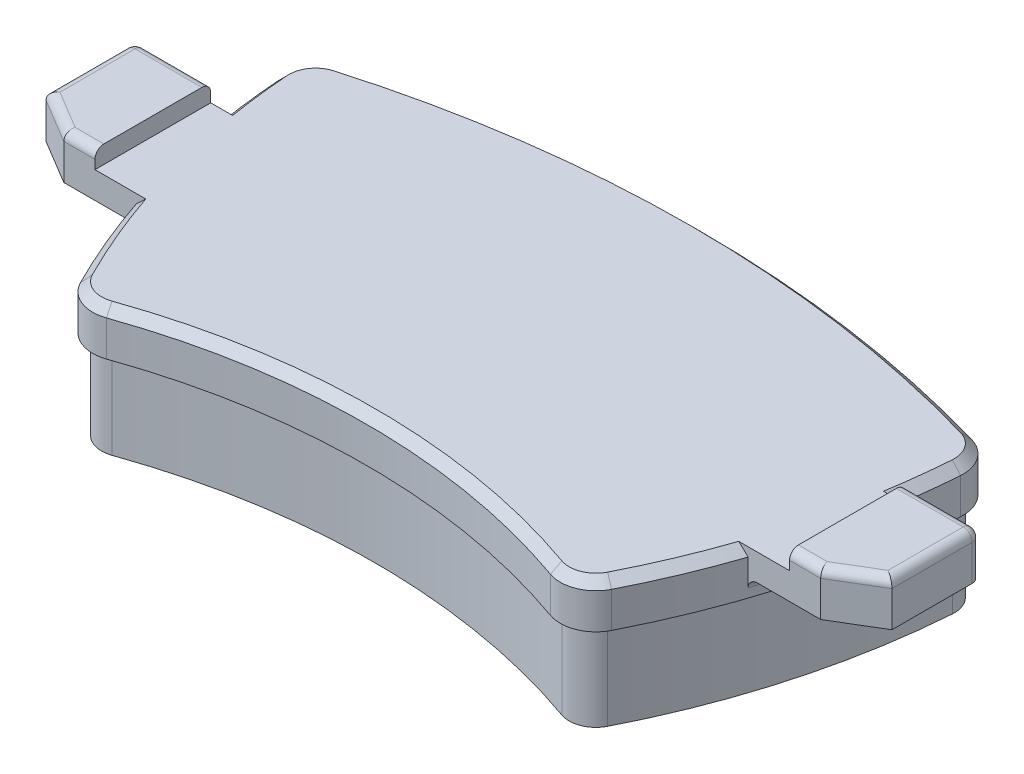
SolidWorks part; units mm, degrees
ref_plane "Front Plane" through (0, 0, 0) normal (0, 0, 1) x (1, 0, 0)
ref_plane "Top Plane" through (0, 0, 0) normal (0, 1, 0) x (1, 0, 0)
ref_plane "Right Plane" through (0, 0, 0) normal (1, 0, 0) x (0, 0, -1)
sketch "Szkic1" plane through (0, 0, 0) normal (0, 1, 0) x (1, 0, 0)
  line L0 (0, -17.533) -> (0, 17.533) construction
  line L5 (-37.5, -17.533) -> (37.5, 17.533) construction
  line L6 (-37.5, 17.533) -> (37.5, -17.533) construction
  line L8 (-37.5749, -16.8044) -> (37.5749, -16.8044)
  line L9 (-37.5749, -16.8044) -> (-37.5749, 23.1956)
  line L10 (-37.5749, 23.1956) -> (37.5749, 23.1956)
  line L11 (37.5749, -16.8044) -> (37.5749, 23.1956)
  arc A0 (-35.1983, 18.2205) -> (35.1983, 18.2205) centre (0, -103.8044) cw
  arc A1 (-28.9322, -15.1612) -> (-37.3587, 15.1176) centre (42.3641, 20.9925) cw
  arc A2 (28.9322, -15.1612) -> (37.3587, 15.1176) centre (-42.3641, 20.9925) ccw
  arc A3 (-25.2594, -16.6338) -> (25.2594, -16.6338) centre (0, -88.3134) cw
  arc A4 (35.1983, 18.2205) -> (37.3587, 15.1176) centre (34.3668, 15.3381) cw
  arc A5 (25.2594, -16.6338) -> (28.9322, -15.1612) centre (26.2565, -13.8044) ccw
  arc A6 (-28.9322, -15.1612) -> (-25.2594, -16.6338) centre (-26.2565, -13.8044) ccw
  arc A7 (-37.3587, 15.1176) -> (-35.1983, 18.2205) centre (-34.3668, 15.3381) cw
  point P0 (0, 0)
  point P6 (27.679, -17.533)
  point P8 (-27.679, -17.533)
  point P21 (27.679, -17.533)
  point P24 (-27.679, -17.533)
  dimension "D3" = 3
  dimension "D5" = 79.939
  dimension "D4" = 127
  dimension "D6" = 76
  dimension "D1" = 75
  dimension "D7" = 26.2565
  dimension "D8" = 75.1498
  dimension "D9" = 40
extrude "Dodanie-wyciągnięcie2" add sketch "Szkic1" along normal blind 10 contours A0 A4 A2 A5 A3 A6 A1 A7
sketch "Szkic3" plane through (0, 10, 0) normal (0, 1, 0) x (1, 0, 0)
  arc A16 (-35.4754, 19.1814) -> (-38.356, 15.0441) centre (-34.3668, 15.3381) ccw
  arc A17 (-38.356, 15.0441) -> (-29.824, -15.6134) centre (42.3641, 20.9925) ccw
  arc A18 (-29.824, -15.6134) -> (-24.9271, -17.577) centre (-26.2565, -13.8044) ccw
  arc A19 (24.9271, -17.577) -> (-24.9271, -17.577) centre (0, -88.3134) ccw
  arc A20 (24.9271, -17.577) -> (29.824, -15.6134) centre (26.2565, -13.8044) ccw
  arc A21 (29.824, -15.6134) -> (38.356, 15.0441) centre (-42.3641, 20.9925) ccw
  arc A22 (38.356, 15.0441) -> (35.4754, 19.1814) centre (34.3668, 15.3381) ccw
  arc A23 (35.4754, 19.1814) -> (-35.4754, 19.1814) centre (0, -103.8044) ccw
  arc A24 (-35.4754, 19.1814) -> (-38.356, 15.0441) centre (-34.3668, 15.3381) ccw
  arc A25 (-38.356, 15.0441) -> (-29.824, -15.6134) centre (42.3641, 20.9925) ccw
  arc A26 (-29.824, -15.6134) -> (-24.9271, -17.577) centre (-26.2565, -13.8044) ccw
  arc A27 (24.9271, -17.577) -> (-24.9271, -17.577) centre (0, -88.3134) ccw
  arc A28 (24.9271, -17.577) -> (29.824, -15.6134) centre (26.2565, -13.8044) ccw
  arc A29 (29.824, -15.6134) -> (38.356, 15.0441) centre (-42.3641, 20.9925) ccw
  arc A30 (38.356, 15.0441) -> (35.4754, 19.1814) centre (34.3668, 15.3381) ccw
  arc A31 (35.4754, 19.1814) -> (-35.4754, 19.1814) centre (0, -103.8044) ccw
  dimension "D1" = 1
extrude "Dodanie-wyciągnięcie3" add sketch "Szkic3" along normal blind 5
sketch "Szkic4" plane through (0, 15, 0) normal (0, 1, 0) x (1, 0, 0)
  line L0 (-34.3538, -4.8044) -> (-38.3278, -4.8044)
  line L1 (-37.5569, 8.1956) -> (-46.5, 8.1956)
  line L3 (-38.3278, -4.8044) -> (-42.5, -4.8044)
  line L4 (-47.5, 7.1956) -> (-47.5, -1.8044)
  line L5 (-42.5, -4.8044) -> (-47.5, -1.8044)
  line L6 (0, -13.3134) -> (0, 35.5288) construction
  line L7 (42.5, -4.8044) -> (47.5, -1.8044)
  line L8 (47.5, 7.1956) -> (47.5, -1.8044)
  line L9 (38.3278, -4.8044) -> (42.5, -4.8044)
  line L10 (37.5569, 8.1956) -> (46.5, 8.1956)
  line L11 (34.3538, -4.8044) -> (38.3278, -4.8044)
  line L12 (53.0989, -17.8044) -> (-74.5075, -17.8044)
  arc A0 (-38.356, 15.0441) -> (-29.824, -15.6134) centre (42.3641, 20.9925) ccw construction
  arc A1 (-37.5569, 8.1956) -> (-34.3538, -4.8044) centre (42.3641, 20.9925) ccw
  arc A2 (24.9271, -17.577) -> (-24.9271, -17.577) centre (0, -88.3134) ccw construction
  arc A4 (37.5569, 8.1956) -> (34.3538, -4.8044) centre (-42.3641, 20.9925) cw
  arc A5 (47.5, 7.1956) -> (46.5, 8.1956) centre (46.5, 7.1956) ccw
  arc A6 (-46.5, 8.1956) -> (-47.5, 7.1956) centre (-46.5, 7.1956) ccw
  arc A7 (-29.824, -15.6134) -> (-24.9271, -17.577) centre (-26.2565, -13.8044) ccw construction
  arc A8 (24.9271, -17.577) -> (29.824, -15.6134) centre (26.2565, -13.8044) ccw construction
  point P30 (47.5, 8.1956)
  point P33 (-47.5, 8.1956)
  arc M14 (29.824, -15.6134) -> (38.356, 15.0441) centre (-42.3641, 20.9925) ccw
  dimension "D1" = 5
  dimension "D4" = 1
  dimension "D2" = 95
  dimension "D5" = 13
  dimension "D6" = 10
  dimension "D7" = 26
extrude "Dodanie-wyciągnięcie4" add sketch "Szkic4" against normal blind 3 and the other way blind 2 contours L11 L9 L7 L8 L10 M14 | L4 L5 L3 L0 A1 L1 A6 region at (41.5596, 15, -1.6589)
chamfer "Sfazowanie2" distance 1 angle 45 10 edges at (-38.0294, 15, -11.6113) (-37.6495, 15, -17.6236) (0, 15, -24.1956) (37.6495, 15, -17.6236) (38.0294, 15, -11.6113) (32.2848, 15, 10.291) (27.7452, 15, 17.517) (0, 15, 13.3134) (-27.7452, 15, 17.517) (-32.2848, 15, 10.291)
fillet "Zaokrąglenie2" radius 1 13 edges at (-36.2246, 12, -1.6293) (-36.2246, 15, -1.6293) (-38.4269, 17, 4.8044) (-45, 17, 3.3044) (-47.5, 17, -2.6956) (-42.0284, 17, -8.1956) (42.0284, 17, -8.1956) (47.5, 17, -2.6956) (45, 17, 3.3044) (38.4269, 17, 4.8044) (36.2246, 12, -1.6293) (36.2246, 15, -1.6293) (36.2246, 17, -1.6293) tangent propagation no
sketch "Szkic5" plane through (0, 15, 0) normal (0, 1, 0) x (1, 0, 0)
  line L0 (0, -29.6497) -> (0, 17.7496) construction
  line L5 (-39, 17.7496) -> (39, 17.7496)
  line L6 (-39, 17.7496) -> (-39, -29.6497)
  line L7 (-39, -29.6497) -> (39, -29.6497)
  line L8 (39, 17.7496) -> (39, -29.6497)
  line L9 (-47.5, -1.8044) -> (-47.5, 7.1956) construction
  line L10 (47.5, 7.1956) -> (47.5, -1.8044) construction
  dimension "D1" = 78
extrude "Wytnij-wyciągnięcie1" cut sketch "Szkic5" along normal blind 10
equation "\"2mm2`\"=10"
